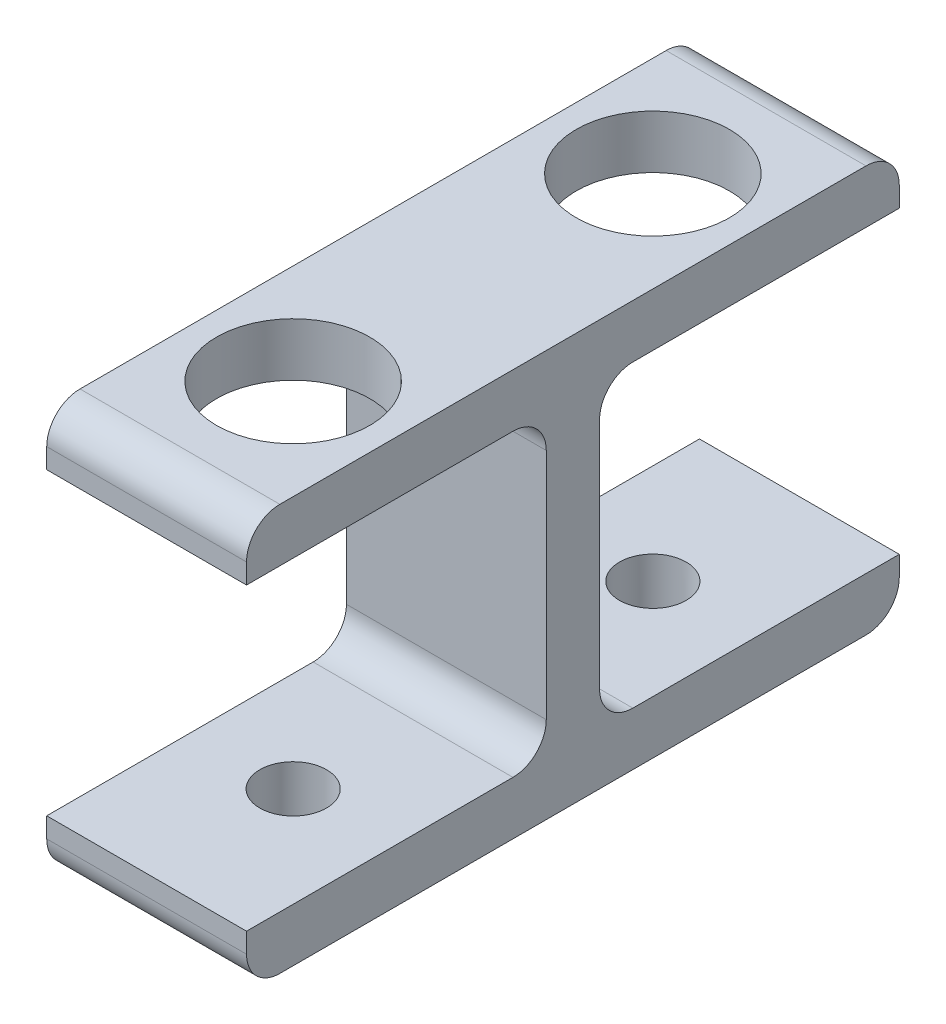
SolidWorks part; units mm, degrees
ref_plane "Front Plane" through (0, 0, 0) normal (0, 0, 1) x (1, 0, 0)
ref_plane "Top Plane" through (0, 0, 0) normal (0, 1, 0) x (1, 0, 0)
ref_plane "Right Plane" through (0, 0, 0) normal (1, 0, 0) x (0, 0, -1)
sketch "Sketch1" plane through (0, 0, 0) normal (1, 0, 0) x (0, 0, -1)
  line L0 (0, 0) -> (45, 0)
  line L1 (45, 0) -> (45, -45)
  line L2 (45, -45) -> (0, -45)
  line L3 (0, -45) -> (0, -53)
  line L4 (0, -53) -> (49, -53)
  line L5 (49, -53) -> (49, 8)
  line L6 (49, 8) -> (0, 8)
  line L7 (0, 8) -> (0, 0)
  dimension "D1" = 45
  dimension "D2" = 45
  dimension "D3" = 8
  dimension "D4" = 4
extrude "Boss-Extrude1" add sketch "Sketch1" along normal blind 30 contours L0 L1 L2 L3 L4 L5 L6 L7
sketch "Sketch2" plane through (0, 8, 0) normal (0, 1, 0) x (1, 0, 0)
  line L0 (30, 0) -> (0, 0) construction
  circle A0 centre (15, 22) radius 11.5
  point P2 (15, 0)
  dimension "D1" = 23
  dimension "D2" = 22
extrude "Cut-Extrude1" cut sketch "Sketch2" against normal up to next
sketch "Sketch3" plane through (0, -45, 0) normal (0, 1, 0) x (1, 0, 0)
  circle A0 centre (15, 22) radius 5
  circle A1 centre (15, 22) radius 11.5 construction
  dimension "D1" = 10
extrude "Cut-Extrude2" cut sketch "Sketch3" against normal up to next contours A0
fillet "Fillet2" radius 5 2 edges at (15, 0, -45) (15, -45, -45)
mirror "Mirror2" about plane through (30, -53, -49) normal (0, 0, 1) of "Fillet2", "Boss-Extrude1", "Cut-Extrude1", "Cut-Extrude2"
fillet "Fillet3" radius 5 4 edges at (15, -53, -98) (15, 8, -98) (15, -53, 0) (15, 8, 0)
